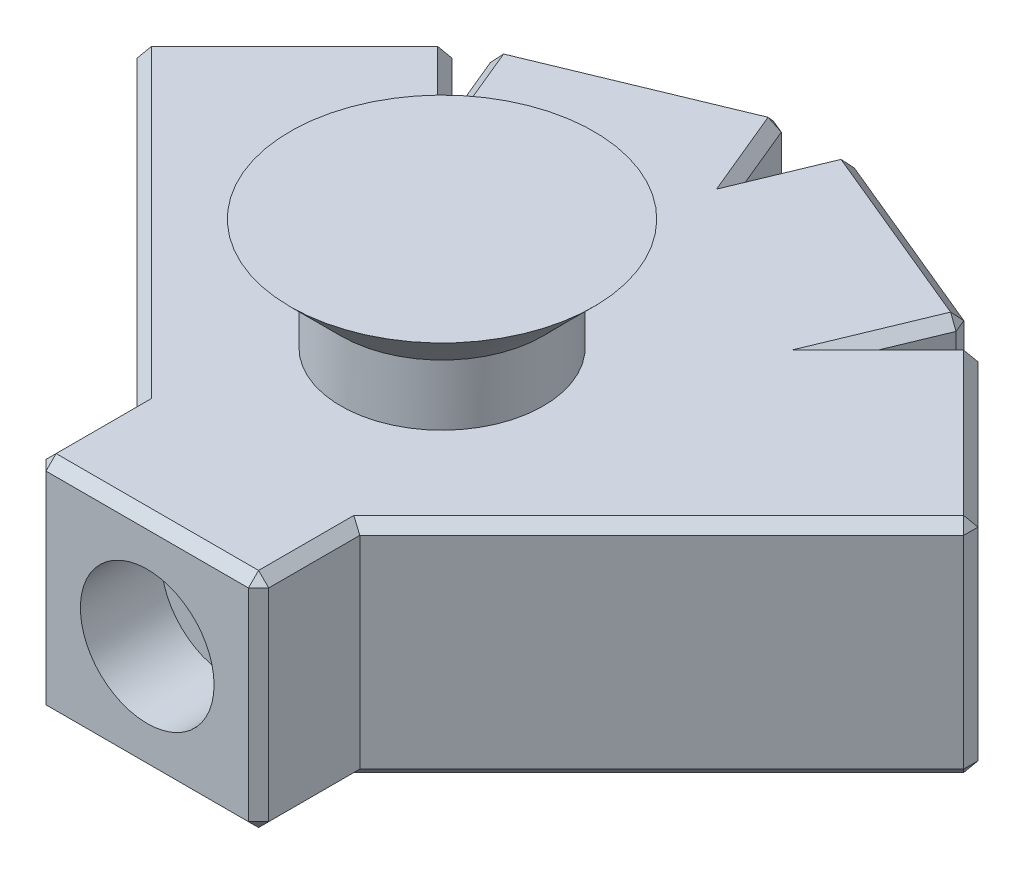
SolidWorks part; units mm, degrees
ref_plane "Front Plane" through (0, 0, 0) normal (0, 0, 1) x (1, 0, 0)
ref_plane "Top Plane" through (0, 0, 0) normal (0, 1, 0) x (1, 0, 0)
ref_plane "Right Plane" through (0, 0, 0) normal (1, 0, 0) x (0, 0, -1)
sketch "Sketch2" plane through (0, 0, 0) normal (0, 1, 0) x (1, 0, 0)
  line L0 (0, 24.4285) -> (-10.1627, 20.219)
  line L1 (-10.1627, 20.219) -> (-17.9408, 12.4408)
  line L2 (-17.9408, 12.4408) -> (-5.5, 0)
  line L3 (-5.5, 0) -> (5.5, 0)
  line L4 (0, 0) -> (0, 24.4285) construction
  line L5 (17.9408, 12.4408) -> (5.5, 0)
  line L6 (10.1627, 20.219) -> (17.9408, 12.4408)
  line L7 (0, 24.4285) -> (10.1627, 20.219)
  line L8 (0, 24.4285) -> (51.7778, 24.4285) construction
  point P9 (0, 0)
  dimension "D1" = 22.5
  dimension "D2" = 45
  dimension "D3" = 11
extrude "Boss-Extrude1" add sketch "Sketch2" along normal blind 11
sketch "Sketch5" plane through (15.1908, 0, -15.1908) normal (0.7071, 0, -0.7071) x (-0.7071, 0, -0.7071)
  line L0 (-3.8891, 0) -> (7.1109, 11) construction
  circle A0 centre (1.6109, 5.5) radius 1.25
  dimension "D1" = 2.5
extrude "Cut-Extrude3" cut sketch "Sketch5" against normal blind 21
sketch "Sketch6" plane through (8.6368, 0, -20.8511) normal (0.3827, 0, -0.9239) x (-0.9239, 0, -0.3827)
  line L0 (-1.6516, 0) -> (9.3484, 11) construction
  circle A0 centre (3.8484, 5.5) radius 1.25
  dimension "D1" = 2.5
extrude "Cut-Extrude4" cut sketch "Sketch6" against normal blind 14
sketch "Sketch7" plane through (-8.6368, 0, -20.8511) normal (-0.3827, 0, -0.9239) x (-0.9239, 0, 0.3827)
  line L0 (-9.3484, 0) -> (1.6516, 11) construction
  circle A0 centre (-3.8484, 5.5) radius 1.25
  dimension "D1" = 2.5
extrude "Cut-Extrude5" cut sketch "Sketch7" against normal blind 14
sketch "Sketch8" plane through (-15.1908, 0, -15.1908) normal (-0.7071, 0, -0.7071) x (-0.7071, 0, 0.7071)
  line L0 (-7.1109, 0) -> (3.8891, 11) construction
  circle A0 centre (-1.6109, 5.5) radius 1.25
  dimension "D1" = 2.5
extrude "Cut-Extrude6" cut sketch "Sketch8" against normal blind 21
sketch "Sketch9" plane through (0, 0, 0) normal (0, 0, 1) x (1, 0, 0)
  line L1 (-5.5, 11) -> (5.5, 11)
  line L2 (-5.5, 11) -> (-5.5, 0)
  line L3 (-5.5, 0) -> (5.5, 0)
  line L4 (5.5, 11) -> (5.5, 0)
extrude "Boss-Extrude2" add sketch "Sketch9" along normal blind 5
sketch "Sketch10" plane through (0, 0, 5) normal (0, 0, 1) x (1, 0, 0)
  line L0 (-5.5, 0) -> (5.5, 11) construction
  circle A0 centre (0, 5.5) radius 1.25
  dimension "D1" = 2.5
extrude "Cut-Extrude7" cut sketch "Sketch10" against normal blind 16
sketch "Sketch12" plane through (0, 0, 5) normal (0, 0, 1) x (1, 0, 0)
  circle A0 centre (0, 5.5) radius 3.302
  dimension "D1" = 6.604
extrude "Cut-Extrude9" cut sketch "Sketch12" against normal blind 4
sketch "Sketch18" plane through (15.1908, 0, -15.1908) normal (0.7071, 0, -0.7071) x (-0.7071, 0, -0.7071)
  line L1 (-3.8891, 11) -> (7.1109, 11)
  line L2 (-3.8891, 11) -> (-3.8891, 0)
  line L3 (-3.8891, 0) -> (7.1109, 0)
  line L4 (7.1109, 11) -> (7.1109, 0)
  circle A0 centre (1.6109, 5.5) radius 3.302
  dimension "D1" = 6.604
extrude "Boss-Extrude3" add sketch "Sketch18" along normal blind 4 contours L2 L1 L4 L3 | A0
sketch "Sketch19" plane through (8.6368, 0, -20.8511) normal (0.3827, 0, -0.9239) x (-0.9239, 0, -0.3827)
  line L1 (-1.6516, 11) -> (9.3484, 11)
  line L2 (-1.6516, 11) -> (-1.6516, 0)
  line L3 (-1.6516, 0) -> (9.3484, 0)
  line L4 (9.3484, 11) -> (9.3484, 0)
  circle A0 centre (3.8484, 5.5) radius 3.302
  dimension "D1" = 6.604
extrude "Boss-Extrude4" add sketch "Sketch19" along normal blind 4
sketch "Sketch20" plane through (-8.6368, 0, -20.8511) normal (-0.3827, 0, -0.9239) x (-0.9239, 0, 0.3827)
  line L2 (-9.3484, 11) -> (1.6516, 11)
  line L3 (-9.3484, 11) -> (-9.3484, 0)
  line L4 (-9.3484, 0) -> (1.6516, 0)
  line L5 (1.6516, 11) -> (1.6516, 0)
  circle A0 centre (-3.8484, 5.5) radius 3.302
  circle A1 centre (-3.8484, 5.5) radius 1.25 construction
  dimension "D1" = 6.604
extrude "Boss-Extrude5" add sketch "Sketch20" along normal blind 4
sketch "Sketch22" plane through (-15.1908, 0, -15.1908) normal (-0.7071, 0, -0.7071) x (-0.7071, 0, 0.7071)
  line L1 (-7.1109, 11) -> (3.8891, 11)
  line L2 (-7.1109, 11) -> (-7.1109, 0)
  line L3 (-7.1109, 0) -> (3.8891, 0)
  line L4 (3.8891, 11) -> (3.8891, 0)
  circle A0 centre (-1.6109, 5.5) radius 3.302
  dimension "D1" = 6.604
extrude "Boss-Extrude7" add sketch "Sketch22" along normal blind 4
chamfer "Chamfer1" distance 0.5 angle 45 40 edges at (16.8802, 11, -19.1584) (5.5, 11, 2.5) (0, 11, 5) (-5.5, 11, 2.5) (-16.8802, 11, -19.1584) (-11.5769, 11, -21.6332) (-10.928, 11, -22.0668) (-6.6121, 11, -26.0193) (-0.7654, 11, -26.2763) (0.7654, 11, -26.2763) (6.6121, 11, -26.0193) (10.928, 11, -22.0668) (11.5769, 11, -21.6332) (-5.5, 0, 2.5) (-5.5, 5.5, 5) (0, 0, 5) (5.5, 5.5, 5) (5.5, 0, 2.5) (-20.7693, 5.5, -15.2693) (-16.8802, 0, -19.1584) (-12.9911, 5.5, -23.0475) (-11.5769, 0, -21.6332) (-10.928, 0, -22.0668) (-11.6934, 5.5, -23.9145) (-6.6121, 0, -26.0193) (-1.5307, 5.5, -28.1241) (-0.7654, 0, -26.2763) (0.7654, 0, -26.2763) (1.5307, 5.5, -28.1241) (6.6121, 0, -26.0193) (11.6934, 5.5, -23.9145) (10.928, 0, -22.0668) (11.5769, 0, -21.6332) (12.9911, 5.5, -23.0475) (16.8802, 0, -19.1584) (20.7693, 5.5, -15.2693) (13.1346, 11, -7.6346) (-13.1346, 11, -7.6346) (-13.1346, 0, -7.6346) (13.1346, 0, -7.6346)
sketch "Sketch24" plane through (0, 11, 0) normal (0, 1, 0) x (1, 0, 0)
  line L0 (0, 23.122) -> (0, -4.5) construction
  line L1 (-5, -4.5) -> (5, -4.5) construction
  circle A0 centre (0, 9.5631) radius 5
  dimension "D1" = 10
extrude "Boss-Extrude8" add sketch "Sketch24" along normal blind 3
sketch "Sketch25" plane through (0, 14, 0) normal (0, 1, 0) x (1, 0, 0)
  circle A0 centre (0, 9.5631) radius 7.5
  dimension "D1" = 15
extrude "Boss-Extrude9" add sketch "Sketch25" along normal blind 2.5
chamfer "Chamfer2" distance 2.5 angle 45 1 edges at (0, 14, -2.0631)
